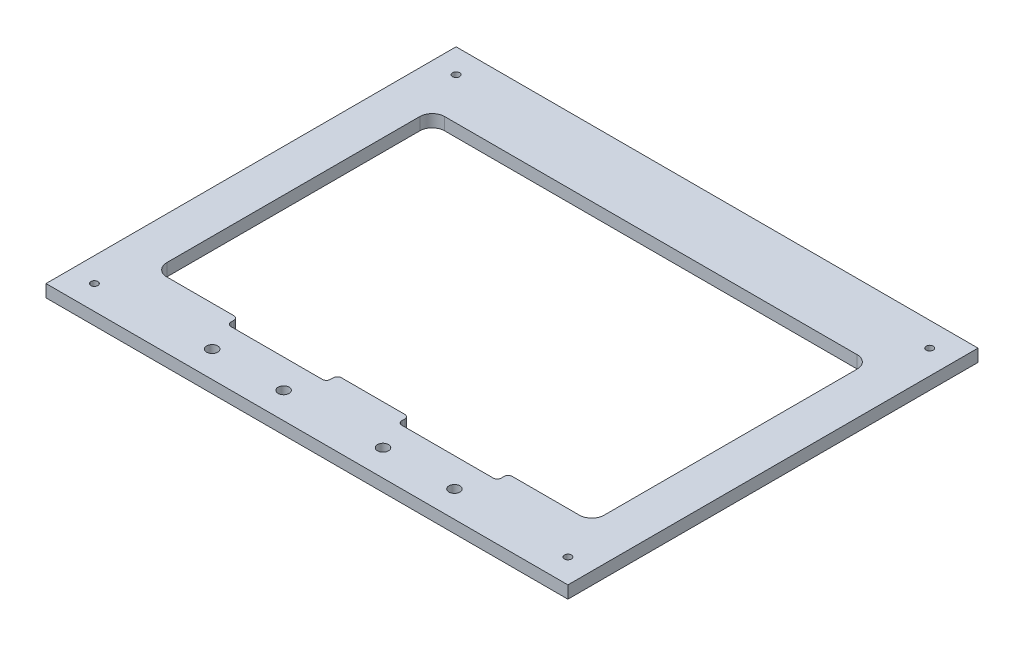
SolidWorks part; units mm, degrees
material "Acrylic (Medium-high impact)"
ref_plane "Front Plane" through (0, 0, 0) normal (0, 0, 1) x (1, 0, 0)
ref_plane "Top Plane" through (0, 0, 0) normal (0, 1, 0) x (1, 0, 0)
ref_plane "Right Plane" through (0, 0, 0) normal (1, 0, 0) x (0, 0, -1)
sketch "Sketch1" plane through (0, 0, 0) normal (0, 1, 0) x (1, 0, 0)
  line L1 (-133.35, 104.775) -> (133.35, 104.775)
  line L2 (-133.35, 104.775) -> (-133.35, -104.775)
  line L3 (-133.35, -104.775) -> (133.35, -104.775)
  line L4 (133.35, 104.775) -> (133.35, -104.775)
  line L5 (-133.35, 104.775) -> (133.35, -104.775) construction
  line L6 (-133.35, -104.775) -> (133.35, 104.775) construction
  point P0 (0, 0)
  dimension "D1" = 209.55
  dimension "D2" = 266.7
extrude "Boss-Extrude1" add sketch "Sketch1" along normal blind 6.35
hole_wizard "M3 Clearance Hole1" positions "Sketch2" profile "Sketch3" hole size "M3" standard "ANSI Metric" end condition through all
sketch "Sketch2" plane through (0, 6.35, 0) normal (0, 1, 0) x (1, 0, 0)
  line L0 (-133.35, -104.775) -> (133.35, -104.775) construction
  line L1 (133.35, -104.775) -> (133.35, 104.775) construction
  line L2 (133.35, 104.775) -> (-133.35, 104.775) construction
  line L3 (-133.35, 104.775) -> (-133.35, -104.775) construction
  point P0 (121.0056, -92.4306)
  point P2 (-121.0056, -92.4306)
  point P4 (-121.0056, 92.4306)
  point P6 (121.0056, 92.4306)
  dimension "D1" = 12.3444
  dimension "D2" = 12.3444
  dimension "D3" = 12.3444
  dimension "D4" = 12.3444
sketch "Sketch3" plane through (121.0056, 6.35, 92.4306) normal (1, 0, 0) x (0, 0, 1)
  line L0 (0, 0) -> (0, 6.35)
  line L1 (0, 6.35) -> (1.8, 6.35)
  line L2 (1.8, 6.35) -> (1.8, 0)
  line L5 (1.8, 0) -> (0, 0)
  line L11 (0, -6.35) -> (0, 107.95) construction
  dimension "Thru Hole Dia." = 3.6
  dimension "Thru Hole Depth" = 6.35
sketch "Sketch4" plane through (0, 6.35, 0) normal (0, 1, 0) x (1, 0, 0)
  line L0 (-133.35, 104.775) -> (-133.35, -104.775) construction
  line L1 (111.76, -70.993) -> (-111.76, -70.993)
  line L2 (111.76, -70.993) -> (111.76, 70.993)
  line L3 (111.76, 70.993) -> (-111.76, 70.993)
  line L4 (-111.76, -70.993) -> (-111.76, 70.993)
  line L5 (111.76, -70.993) -> (-111.76, 70.993) construction
  line L6 (111.76, 70.993) -> (-111.76, -70.993) construction
  line L7 (133.35, 104.775) -> (-133.35, 104.775) construction
  point P0 (0, 0)
  dimension "D1" = 21.59
  dimension "D2" = 33.782
extrude "Cut-Extrude1" cut sketch "Sketch4" against normal through all
hole_wizard "#10 Clearance Hole1" positions "Sketch5" profile "Sketch6" hole size "#10" standard "ANSI Inch" end condition through all
sketch "Sketch5" plane through (0, 6.35, 0) normal (0, 1, 0) x (1, 0, 0)
  line L0 (-61.9125, -91.313) -> (-25.4, -91.313) construction
  line L2 (25.4, -91.313) -> (61.9125, -91.313) construction
  line L4 (-25.4, -91.313) -> (25.4, -91.313) construction
  line L5 (-111.76, -70.993) -> (111.76, -70.993) construction
  point P0 (-61.9125, -91.313)
  point P4 (-25.4, -91.313)
  point P6 (25.4, -91.313)
  point P10 (61.9125, -91.313)
  point P29 (0, -91.313)
  point P34 (0, 0)
  point P35 (0, 0)
  dimension "D1" = 36.5125
  dimension "D2" = 36.5125
  dimension "D3" = 50.8
  dimension "D4" = 20.32
sketch "Sketch6" plane through (-61.9125, 6.35, 91.313) normal (1, 0, 0) x (0, 0, 1)
  line L0 (0, 0) -> (0, 6.35)
  line L1 (0, 6.35) -> (2.8067, 6.35)
  line L2 (2.8067, 6.35) -> (2.8067, 0)
  line L5 (2.8067, 0) -> (0, 0)
  line L11 (0, -6.35) -> (0, 107.95) construction
  dimension "Thru Hole Dia." = 5.6134
  dimension "Thru Hole Depth" = 6.35
sketch "Sketch7" plane through (0, 6.35, 0) normal (0, 1, 0) x (1, 0, 0)
  line L0 (-111.76, -70.993) -> (111.76, -70.993) construction
  line L1 (-69.0563, -76.581) -> (-18.2563, -76.581)
  line L2 (-69.0563, -76.581) -> (-69.0563, -70.993)
  line L3 (-69.0563, -70.993) -> (-18.2563, -70.993)
  line L4 (-18.2563, -76.581) -> (-18.2563, -70.993)
  line L5 (-69.0563, -76.581) -> (-18.2563, -70.993) construction
  line L6 (-69.0563, -70.993) -> (-18.2563, -76.581) construction
  line L7 (-43.6562, -73.787) -> (-43.6562, -91.313) construction
  line L8 (18.2562, -76.581) -> (69.0562, -76.581)
  line L9 (18.2562, -76.581) -> (18.2562, -70.993)
  line L10 (18.2562, -70.993) -> (69.0562, -70.993)
  line L11 (69.0562, -76.581) -> (69.0562, -70.993)
  line L12 (18.2562, -76.581) -> (69.0562, -70.993) construction
  line L13 (18.2562, -70.993) -> (69.0562, -76.581) construction
  line L14 (43.6562, -73.787) -> (43.6562, -91.313) construction
  line L15 (-61.9125, -91.313) -> (-25.4, -91.313) construction
  line L16 (25.4, -91.313) -> (61.9125, -91.313) construction
  point P0 (-43.6563, -73.787)
  point P7 (43.6562, -73.787)
  point P26 (0, 0)
  point P27 (0, 0)
  dimension "D3" = 50.8
  dimension "D4" = 5.588
extrude "Cut-Extrude2" cut sketch "Sketch7" against normal through all
fillet "Fillet1" radius 6.35 4 edges at (111.76, 3.175, -70.993) (111.76, 3.175, 70.993) (-111.76, 3.175, 70.993) (-111.76, 3.175, -70.993)
fillet "Fillet2" radius 2.032 8 edges at (69.0562, 3.175, 70.993) (69.0562, 3.175, 76.581) (18.2562, 3.175, 76.581) (18.2562, 3.175, 70.993) (-18.2563, 3.175, 70.993) (-18.2563, 3.175, 76.581) (-69.0562, 3.175, 70.993) (-69.0563, 3.175, 76.581)
